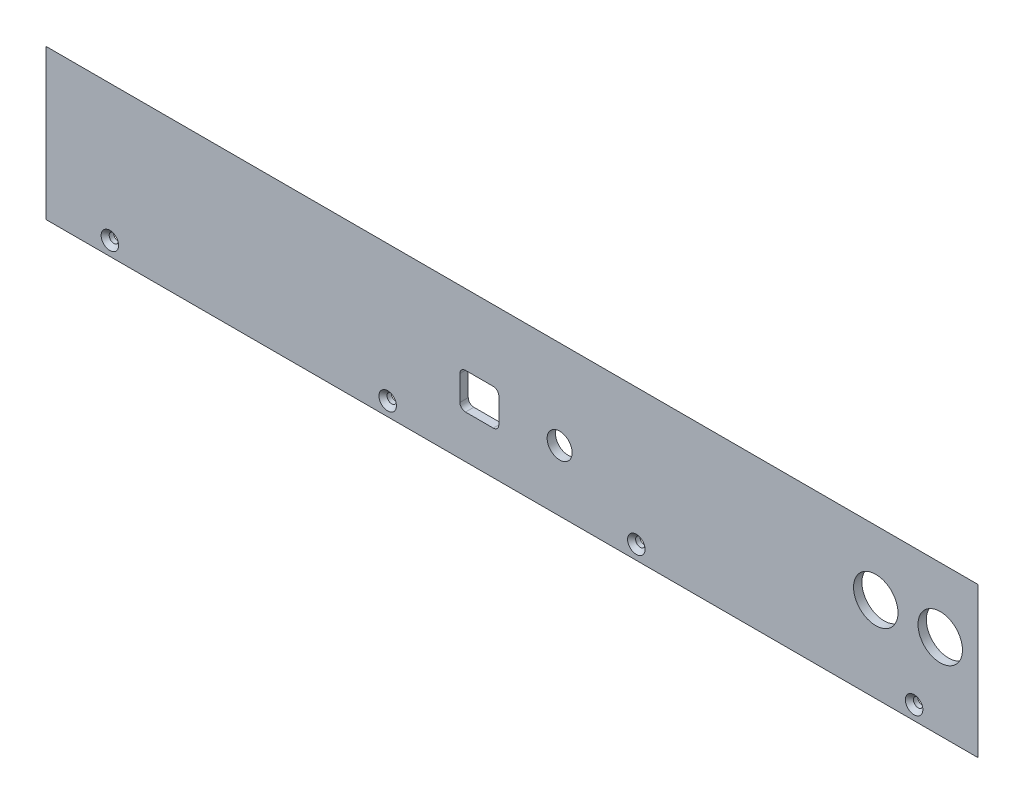
SolidWorks part; units mm, degrees
ref_plane "Front Plane" through (0, 0, 0) normal (0, 0, 1) x (1, 0, 0)
ref_plane "Top Plane" through (0, 0, 0) normal (0, 1, 0) x (1, 0, 0)
ref_plane "Right Plane" through (0, 0, 0) normal (1, 0, 0) x (0, 0, -1)
sketch "Sketch1" plane through (0, 0, 0) normal (0, 0, 1) x (1, 0, 0)
  line L1 (0, 0) -> (335.5, 0)
  line L2 (0, 0) -> (0, 54)
  line L3 (0, 54) -> (335.5, 54)
  line L4 (335.5, 0) -> (335.5, 54)
  dimension "D1" = 54
  dimension "D2" = 335.5
extrude "Boss-Extrude1" add sketch "Sketch1" along normal blind 3
chamfer "Chamfer1" distance 3 angle 45 3 edges at (0, 27, 0) (167.75, 54, 0) (335.5, 27, 0)
sketch "Sketch2" plane through (0, 0, 3) normal (0, 0, 1) x (1, 0, 0)
  line L0 (0, 5) -> (335.5, 5) construction
  line L1 (0, 54) -> (0, 0) construction
  line L2 (335.5, 0) -> (335.5, 54) construction
  line L3 (0, 0) -> (335.5, 0) construction
  point P8 (123, 5)
  point P9 (23, 5)
  point P10 (212.5, 5)
  point P11 (312.5, 5)
  dimension "D1" = 5
  dimension "D2" = 23
  dimension "D3" = 100
  dimension "D4" = 23
  dimension "D5" = 100
hole_wizard "CSK for M3 Flat Head Machine Screw1" positions "Sketch4" profile "Sketch3" countersink size "M3" standard "ANSI Metric" end condition through all
sketch "Sketch4" plane through (0, 0, 3) normal (0, 0, 1) x (1, 0, 0)
  point P0 (23, 5)
  point P3 (123, 5)
  point P6 (212.5, 5)
  point P9 (312.5, 5)
sketch "Sketch3" plane through (23, 5, 3) normal (1, 0, 0) x (0, -1, 0)
  line L0 (0, 0) -> (0, 3)
  line L1 (0, 3) -> (1.7, 3)
  line L2 (1.7, 3) -> (1.7, 1.45)
  line L3 (1.7, 1.45) -> (3.15, 0)
  line L5 (3.15, 0) -> (0, 0)
  line L6 (-1.7, 1.45) -> (-3.15, 0) construction
  line L11 (0, -6.35) -> (0, 107.95) construction
  dimension "Thru Hole Dia." = 3.4
  dimension "Thru Hole Depth" = 3
  dimension "Near C'Sink Dia." = 6.3
  dimension "Near C'Sink Angle" = 90
sketch "Sketch5" plane through (0, 0, 3) normal (0, 0, 1) x (1, 0, 0)
  line L0 (156, 22) -> (184.9, 22) construction
  line L1 (150, 16.5) -> (162, 16.5) construction
  line L2 (150, 16.5) -> (150, 27.5) construction
  line L3 (150, 27.5) -> (162, 27.5) construction
  line L4 (162, 16.5) -> (162, 27.5) construction
  line L5 (150, 16.5) -> (162, 27.5) construction
  line L6 (150, 27.5) -> (162, 16.5) construction
  line L7 (0, 0) -> (335.5, 0) construction
  line L8 (335.5, 0) -> (335.5, 54) construction
  line L9 (298.7, 30.75) -> (321.9, 30.75) construction
  line L10 (321.9, 30.75) -> (321.9, 20) construction
  line L11 (151, 28.5) -> (161, 28.5)
  line L12 (163, 17.5) -> (163, 26.5)
  line L13 (151, 15.5) -> (161, 15.5)
  line L14 (149, 17.5) -> (149, 26.5)
  line L15 (149, 28.5) -> (163, 28.5) construction
  line L16 (163, 15.5) -> (163, 28.5) construction
  line L17 (149, 15.5) -> (163, 15.5) construction
  line L18 (149, 15.5) -> (149, 28.5) construction
  circle A0 centre (184.9, 22) radius 4.5
  circle A1 centre (298.7, 30.75) radius 8
  circle A2 centre (321.9, 30.75) radius 8
  arc A3 (161, 28.5) -> (163, 26.5) centre (161, 26.5) cw
  arc A4 (163, 17.5) -> (161, 15.5) centre (161, 17.5) cw
  arc A5 (151, 15.5) -> (149, 17.5) centre (151, 17.5) cw
  arc A6 (151, 28.5) -> (149, 26.5) centre (151, 26.5) ccw
  point P0 (156, 22)
  point P16 (311.3, 30.75)
  dimension "D1" = 9
  dimension "D7" = 13.6
  dimension "D11" = 16
  dimension "D13" = 2
  dimension "D2" = 12
  dimension "D3" = 11
  dimension "D4" = 22.9
  dimension "D5" = 16.5
  dimension "D6" = 173.5
  dimension "D8" = 23.2
  dimension "D9" = 10.75
  dimension "D10" = 20
  dimension "D12" = 1
extrude "Cut-Extrude1" cut sketch "Sketch5" against normal through all
